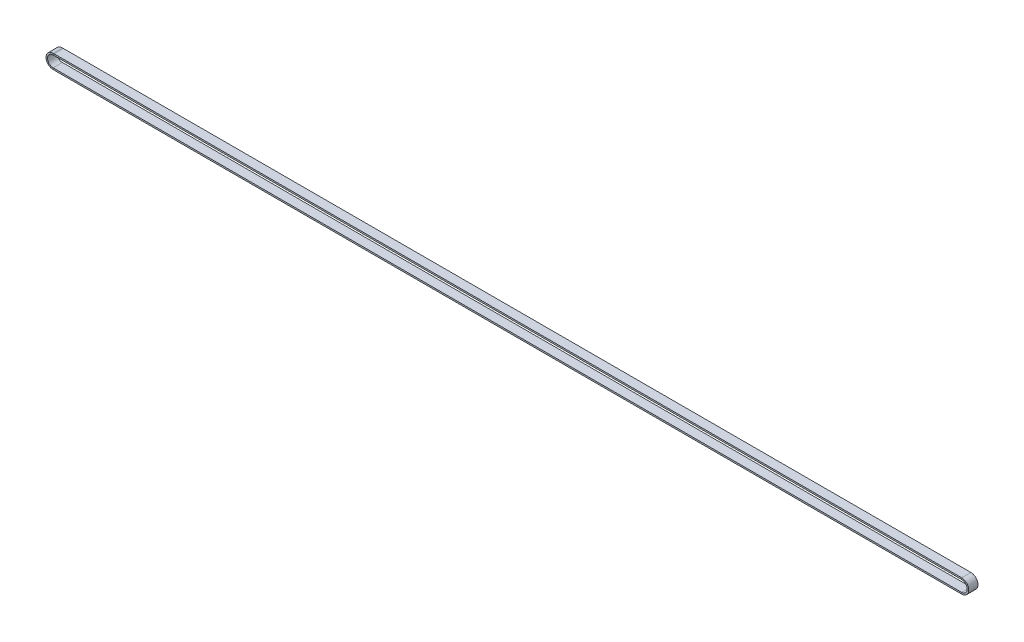
SolidWorks part; units mm, degrees
ref_plane "Front Plane" through (0, 0, 0) normal (0, 0, 1) x (1, 0, 0)
ref_plane "Top Plane" through (0, 0, 0) normal (0, 1, 0) x (1, 0, 0)
ref_plane "Right Plane" through (0, 0, 0) normal (1, 0, 0) x (0, 0, -1)
sketch "Sketch2" plane through (0, 0, -11.7334) normal (0, 0, 1) x (1, 0, 0)
  line L0 (0, 0) -> (1, 0) construction
  line L1 (0, 0) -> (0, 1) construction
  line L2 (-1, -79.3515) -> (883.5206, -79.3515)
  line L3 (883.5206, -93.1515) -> (-1, -93.1515)
  arc A0 (-1, -93.1515) -> (-1, -79.3515) centre (-1, -86.2515) cw
  arc A1 (883.5206, -79.3515) -> (883.5206, -93.1515) centre (883.5206, -86.2515) cw
sketch "Sketch3" plane through (0, 0, 0) normal (1, 0, 0) x (0, 0, -1)
  line L1 (11.7334, -80.8515) -> (2.7334, -80.8515)
  line L2 (11.7334, -80.8515) -> (11.7334, -79.3515)
  line L3 (11.7334, -79.3515) -> (2.7334, -79.3515)
  line L4 (2.7334, -80.8515) -> (2.7334, -79.3515)
  dimension "D1" = 9
  dimension "D2" = 1.5
sweep "Sweep1" add profiles "Sketch3" path "Sketch2"
